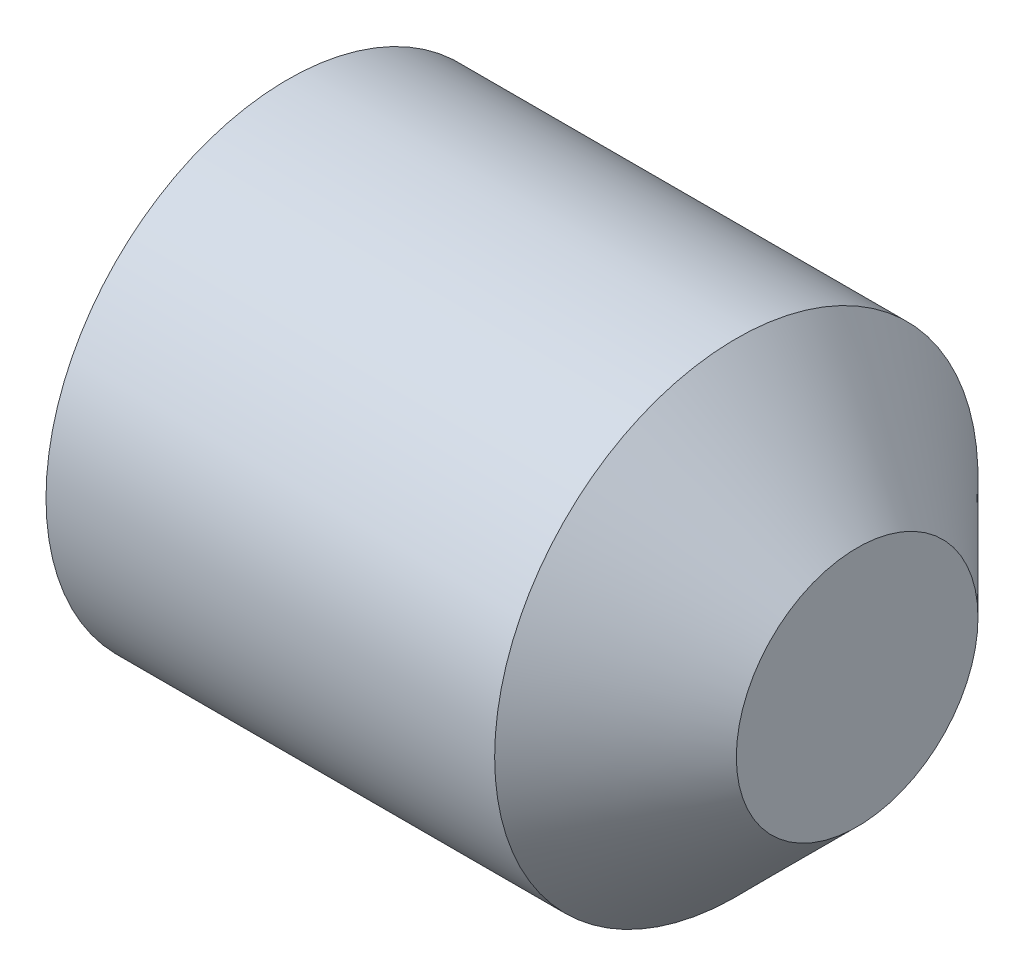
SolidWorks part; units mm, degrees
ref_plane "Front Plane" through (0, 0, 0) normal (0, 0, 1) x (1, 0, 0)
ref_plane "Top Plane" through (0, 0, 0) normal (0, 1, 0) x (1, 0, 0)
ref_plane "Right Plane" through (0, 0, 0) normal (1, 0, 0) x (0, 0, -1)
sketch "BodySke" plane through (0, 0, 0) normal (0, 0, 1) x (1, 0, 0)
  line L0 (0, 0) -> (3.28, 0) construction
  line L1 (2, 0) -> (2, 0.4)
  line L2 (2, 0.4) -> (1.6, 0.8)
  line L3 (1.6, 0.8) -> (0, 0.8)
  line L4 (0, 0.8) -> (0, 0)
  line L5 (0, 0) -> (2, 0)
  line L6 (1.65, 1.0236) -> (1.65, -0.6432) construction
  point P5 (0, 0.601)
  dimension "Minor_dia" = 1.202
  dimension "Advance" = 0.35
revolve "BaseBody" add sketch "BodySke" angle 360 about L0
cosmetic thread "ThreadCosmetic" [suppressed] parameters "Minor_dia"=1.202
sketch "HeadChamferSke" plane through (0, 0, 0) normal (0, 0, 1) x (1, 0, 0)
  line L0 (0, 0) -> (2.4505, 0) construction
  line L1 (0, 0.8) -> (0, 0.601)
  line L2 (0, 0.8) -> (0.1149, 0.8)
  line L3 (0.1149, 0.8) -> (0, 0.601)
  line L4 (1.6, 0.8) -> (0, 0.8) construction
  line L5 (0, 0.8) -> (0, -0.8) construction
  line L6 (0, 0.8) -> (0, 0) construction
  dimension "Angle" = 30
revolve "HeadChamfer" cut sketch "HeadChamferSke" angle 360 about L0
sketch "HexagonSocketSke" plane through (0, 0, 0) normal (-1, 0, 0) x (0, 0, 1)
  line L1 (0, 0.4041) -> (-0.35, 0.2021)
  line L2 (-0.35, 0.2021) -> (-0.35, -0.2021)
  line L3 (-0.35, -0.2021) -> (0, -0.4041)
  line L4 (0, -0.4041) -> (0.35, -0.2021)
  line L5 (0.35, -0.2021) -> (0.35, 0.2021)
  line L6 (0.35, 0.2021) -> (0, 0.4041)
  circle A0 centre (0, 0) radius 0.35 construction
  dimension "Hexagon_Width" = 0.7
extrude "HexagonSocket" cut sketch "HexagonSocketSke" against normal blind 0.7
sketch "ThdSchSke" plane through (0, 0, 0) normal (0, 0, 1) x (1, 0, 0)
  line L0 (0, 0) -> (2.6881, 0) construction
  line L1 (0.2351, 1.0298) -> (0.2351, 0.8)
  line L2 (0.2351, 1.0298) -> (0.4649, 1.0298)
  line L3 (0.4649, 1.0298) -> (0.4649, 0.8)
  line L4 (0.4649, 0.8) -> (0.35, 0.601)
  line L5 (0.35, 0.601) -> (0.2351, 0.8)
  line L6 (1.6, 0.8) -> (0.1149, 0.8) construction
  dimension "D1" = 0.35
revolve "ThreadSchematic" [suppressed] cut sketch "ThdSchSke" angle 360 about L0
pattern_linear "ThdSchPat" [suppressed] count 4 along (1, 0, 0) of bodies 104
equation "\"Minor_dia@ThreadCosmetic\" = \"Minor_dia@BodySke\""
equation "\"D1@ThdSchSke\" = \"Advance@BodySke\""
equation "\"Advance@ThdSchPat\" = \"Advance@BodySke\""
equation "\"D1@ThdSchPat\" =  int( ( \"Length@BodySke\" -  ( \"Diameter@BodySke\" / 2 - \"Chamfer_End@BodySke\" / 2 )  )  / \"Advance@ThdSchPat\" * 0.98  )  "
